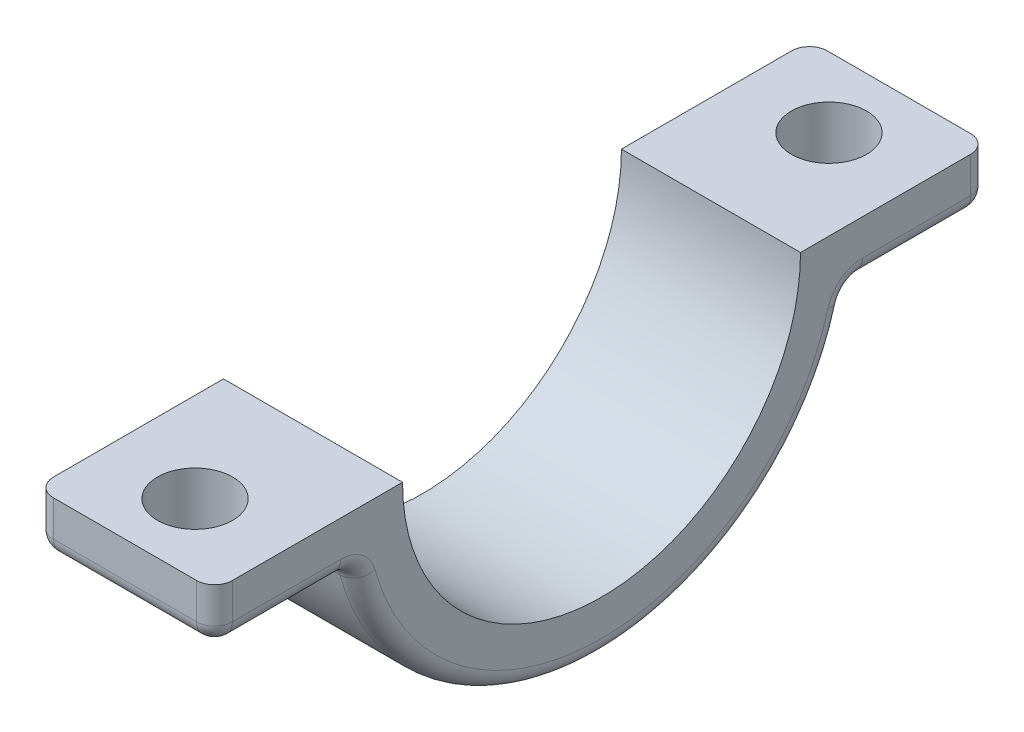
SolidWorks part; units mm, degrees
ref_plane "Front Plane" through (0, 0, 0) normal (0, 0, 1) x (1, 0, 0)
ref_plane "Top Plane" through (0, 0, 0) normal (0, 1, 0) x (1, 0, 0)
ref_plane "Right Plane" through (0, 0, 0) normal (1, 0, 0) x (0, 0, -1)
sketch "Sketch4" plane through (0, 0, 0) normal (1, 0, 0) x (0, 0, -1)
  line L0 (-21.6125, 0) -> (-11.1125, 0)
  line L2 (-21.6125, 0) -> (-21.6125, -3)
  line L3 (-21.6125, -3) -> (-13.7899, -3)
  line L4 (21.6125, 0) -> (21.6125, -3)
  line L5 (13.7899, -3) -> (21.6125, -3)
  line L6 (11.1125, 0) -> (21.6125, 0)
  arc A0 (-11.1125, 0) -> (11.1125, 0) centre (0, 0) ccw
  arc A2 (-13.7899, -3) -> (13.7899, -3) centre (0, 0) ccw
  dimension "D2" = 22.225
extrude "Clamp Extrude" add sketch "Sketch4" along normal blind 10
sketch "Hole" plane through (0, -3, 0) normal (0, -1, 0) x (1, 0, 0)
  line L2 (10, 21.6125) -> (0, 21.6125) construction
  line L3 (10, 13.7899) -> (0, 13.7899) construction
  line L4 (0, 21.6125) -> (0, 13.7899) construction
  line L5 (10, 21.6125) -> (10, 13.7899) construction
  line L6 (0, 0) -> (10, 0)
  line L7 (0, 13.7899) -> (0, -13.7899) construction
  line L8 (10, -13.7899) -> (10, 13.7899) construction
  circle A0 centre (5, 17.7012) radius 2.1
  circle A1 centre (5, -17.7012) radius 2.1
  dimension "D1" = 4.2
  dimension "D2" = 7.8226
  dimension "D3" = 3.9113
  dimension "D4" = 10
  dimension "D5" = 5
extrude "Holes Cut-Extrude" cut sketch "Hole" against normal through all contours A0 | A1 region at (5, -3, 17.7012) region at (5, -3, -17.7012)
fillet "Fillet1" radius 1 14 edges at (10, -3, -17.7012) (0, -3, -17.7012) (10, -14.1125, 0) (0, -14.1125, 0) (0, -1.5, 21.6125) (10, -1.5, 21.6125) (10, -1.5, -21.6125) (0, -1.5, -21.6125) (5, -3, -21.6125) (5, -3, -13.7899) (5, -3, 13.7899) (10, -3, 17.7012) (5, -3, 21.6125) (0, -3, 17.7012)
equation "\"D3@Hole\"=\"D2@Hole\"/2"
equation "\"D5@Hole\"=\"D4@Hole\"/2"
